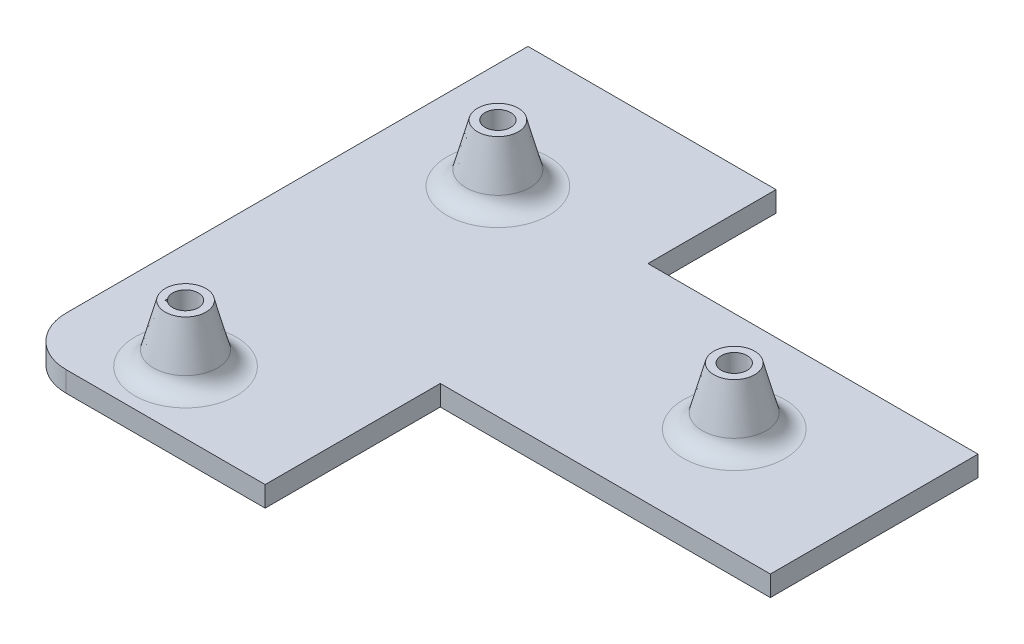
SolidWorks part; units mm, degrees
ref_plane "Front Plane" through (0, 0, 0) normal (0, 0, 1) x (1, 0, 0)
ref_plane "Top Plane" through (0, 0, 0) normal (0, 1, 0) x (1, 0, 0)
ref_plane "Right Plane" through (0, 0, 0) normal (1, 0, 0) x (0, 0, -1)
sketch "Backplane" plane through (0, 0, 0) normal (0, 1, 0) x (1, 0, 0)
  line L0 (-80.645, 87.63) -> (8.255, 87.63)
  line L1 (-106.045, -113.03) -> (106.045, -113.03)
  line L2 (-106.045, -113.03) -> (-106.045, 113.03)
  line L3 (-106.045, 113.03) -> (106.045, 113.03)
  line L4 (106.045, -113.03) -> (106.045, 113.03)
  line L5 (-106.045, -113.03) -> (106.045, 113.03) construction
  line L6 (-106.045, 113.03) -> (106.045, -113.03) construction
  line L7 (-106.045, 113.03) -> (-80.645, 113.03) construction
  line L8 (-106.045, 113.03) -> (-106.045, 87.63) construction
  line L9 (-106.045, 87.63) -> (-80.645, 87.63)
  line L10 (-80.645, 113.03) -> (-80.645, 87.63)
  line L11 (106.045, 113.03) -> (80.645, 113.03) construction
  line L12 (106.045, 113.03) -> (106.045, 87.63) construction
  line L13 (106.045, 87.63) -> (80.645, 87.63)
  line L14 (80.645, 113.03) -> (80.645, 87.63)
  line L15 (8.255, 87.63) -> (8.255, 113.03)
  point P0 (0, 0)
  dimension "D1" = 212.09
  dimension "D2" = 226.06
sketch "Protoboard1" plane through (0, 0, 0) normal (0, 1, 0) x (1, 0, 0)
  line L0 (59.2817, 74.5827) -> (59.2817, 49.1827) construction
  line L1 (-98.1983, 23.7827) -> (59.2817, 23.7827)
  line L2 (-98.1983, 23.7827) -> (-98.1983, 74.5827)
  line L3 (-98.1983, 74.5827) -> (59.2817, 74.5827)
  line L4 (59.2817, 23.7827) -> (59.2817, 74.5827)
  line L5 (-98.1983, 23.7827) -> (59.2817, 74.5827) construction
  line L6 (-98.1983, 74.5827) -> (59.2817, 23.7827) construction
  line L7 (-92.8897, 49.1827) -> (53.9731, 49.1827)
  line L8 (-19.4583, 49.1827) -> (-19.4583, 23.7827) construction
  line L9 (-92.8897, 49.1827) -> (-94.4772, 49.1827)
  circle A4 centre (-94.4772, 49.1827) radius 1.5875
  circle A5 centre (-94.4772, 49.1827) radius 5.5499
  circle A6 centre (55.5606, 49.1827) radius 1.5875
  circle A7 centre (55.5606, 49.1827) radius 5.5499
  circle A8 centre (-94.4772, 49.1827) radius 1.9939
  circle A9 centre (55.5606, 49.1827) radius 1.9939
  point P0 (-19.4583, 49.1827)
  point P9 (-19.4583, 49.1827)
  point P10 (-19.4583, 49.1827)
  dimension "D5" = 3.175
  dimension "D6" = 11.0998
  dimension "D7" = 3.9878
  dimension "D3" = 157.48
  dimension "D1" = 73.4314
  dimension "D2" = 1.5875
sketch "Protoboard2" plane through (0, 0, 0) normal (0, 1, 0) x (1, 0, 0)
  line L0 (58.42, 17.145) -> (58.42, -8.255) construction
  line L1 (-99.06, -33.655) -> (58.42, -33.655)
  line L2 (-99.06, -33.655) -> (-99.06, 17.145)
  line L3 (-99.06, 17.145) -> (58.42, 17.145)
  line L4 (58.42, -33.655) -> (58.42, 17.145)
  line L5 (-99.06, -33.655) -> (58.42, 17.145) construction
  line L6 (-99.06, 17.145) -> (58.42, -33.655) construction
  line L7 (-93.7514, -8.255) -> (53.1114, -8.255)
  line L8 (-20.32, -8.255) -> (-20.32, -33.655) construction
  line L9 (-93.7514, -8.255) -> (-95.3389, -8.255)
  circle A0 centre (-95.3389, -8.255) radius 1.5875
  circle A1 centre (-95.3389, -8.255) radius 5.5499
  circle A4 centre (-95.3389, -8.255) radius 1.9939
  circle A6 centre (54.6989, -8.255) radius 1.5875
  circle A7 centre (54.6989, -8.255) radius 1.9939
  circle A8 centre (54.6989, -8.255) radius 5.5499
  point P0 (-20.32, -8.255)
  point P9 (-20.32, -8.255)
  point P10 (-20.32, -8.255)
  dimension "D5" = 3.175
  dimension "D6" = 11.0998
  dimension "D7" = 3.9878
  dimension "D4" = 1.5875
  dimension "D1" = 157.48
  dimension "D3" = 73.4314
sketch "ADS1256" plane through (0, 0, 0) normal (0, 1, 0) x (1, 0, 0)
  line L0 (83.3697, -5.6387) -> (83.3697, 20.5868)
  line L1 (65.6786, -35.7758) -> (101.0608, -35.7758)
  line L2 (65.6786, -35.7758) -> (65.6786, 24.4984)
  line L3 (65.6786, 24.4984) -> (101.0608, 24.4984)
  line L4 (101.0608, -35.7758) -> (101.0608, 24.4984)
  line L5 (65.6786, -35.7758) -> (101.0608, 24.4984) construction
  line L6 (65.6786, 24.4984) -> (101.0608, -35.7758) construction
  line L7 (83.3697, 20.5868) -> (83.3697, 22.1743)
  line L8 (83.3697, 22.1743) -> (97.0222, 22.1743)
  line L9 (97.0222, 22.1743) -> (98.6097, 22.1743)
  line L10 (83.3697, -5.6387) -> (89.9657, -5.6387) construction
  circle A0 centre (98.6097, 22.1743) radius 1.5875
  circle A1 centre (98.6097, 22.1743) radius 5.5499
  circle A2 centre (68.1297, 22.1743) radius 1.5875
  circle A3 centre (68.1297, 22.1743) radius 5.5499
  circle A4 centre (98.6097, -33.4517) radius 5.5499
  circle A5 centre (98.6097, -33.4517) radius 1.5875
  circle A6 centre (68.1297, -33.4517) radius 1.5875
  circle A7 centre (68.1297, -33.4517) radius 5.5499
  circle A8 centre (98.6097, 22.1743) radius 1.9939
  circle A9 centre (68.1297, 22.1743) radius 1.9939
  circle A10 centre (98.6097, -33.4517) radius 1.9939
  circle A11 centre (68.1297, -33.4517) radius 1.9939
  point P0 (83.3697, -5.6387)
  dimension "D1" = 1.5875
  dimension "D2" = 1.5875
  dimension "D3" = 3.175
  dimension "D4" = 11.0998
  dimension "D5" = 3.9878
sketch "3V_Buck" plane through (0, 0, 0) normal (0, 1, 0) x (1, 0, 0)
  circle A0 centre (88.2115, 54.7666) radius 1.5875
  circle A1 centre (88.2115, 54.7666) radius 5.5499
  circle A2 centre (88.2115, 54.7666) radius 1.9939
  dimension "D1" = 3.175
  dimension "D2" = 11.0998
  dimension "D3" = 3.9878
sketch "Relay" plane through (0, 0, 0) normal (0, 1, 0) x (1, 0, 0)
  line L1 (16.3302, 81.8626) -> (66.6036, 81.8626)
  line L2 (16.3302, 81.8626) -> (16.3302, 108.1272)
  line L3 (16.3302, 108.1272) -> (66.6036, 108.1272)
  line L4 (66.6036, 81.8626) -> (66.6036, 108.1272)
  line L5 (16.3302, 81.8626) -> (66.6036, 108.1272) construction
  line L6 (16.3302, 108.1272) -> (66.6036, 81.8626) construction
  line L7 (41.4669, 94.9949) -> (41.4669, 104.2024)
  line L8 (41.4669, 104.2024) -> (41.4669, 105.7899)
  line L9 (41.4669, 105.7899) -> (62.1298, 105.7899)
  line L10 (62.1298, 105.7899) -> (63.7173, 105.7899)
  line L11 (41.4669, 94.9949) -> (31.7125, 94.9949) construction
  circle A0 centre (63.7173, 105.7899) radius 1.5875
  circle A1 centre (63.7173, 105.7899) radius 5.5499
  circle A2 centre (19.2165, 105.7899) radius 1.5875
  circle A3 centre (19.2165, 105.7899) radius 5.5499
  circle A4 centre (19.2165, 84.1999) radius 1.5875
  circle A5 centre (19.2165, 84.1999) radius 5.5499
  circle A6 centre (63.7173, 84.1999) radius 1.5875
  circle A7 centre (63.7173, 84.1999) radius 5.5499
  circle A8 centre (63.7173, 105.7899) radius 1.9939
  circle A9 centre (19.2165, 105.7899) radius 1.9939
  circle A10 centre (19.2165, 84.1999) radius 1.9939
  circle A11 centre (63.7173, 84.1999) radius 1.9939
  dimension "D4" = 3.175
  dimension "D5" = 11.0998
  dimension "D6" = 3.9878
  dimension "D1" = 1.5875
  dimension "D2" = 20.6629
  dimension "D3" = 1.5875
sketch "ServoBoard" plane through (0, 0, 0) normal (0, 1, 0) x (1, 0, 0)
  line L0 (-89.6011, -103.339) -> (-89.6011, -58.0508)
  line L1 (-103.5076, -105.5869) -> (-34.6228, -105.5869)
  line L2 (-103.5076, -105.5869) -> (-103.5076, -52.1961)
  line L3 (-103.5076, -52.1961) -> (-34.6228, -52.1961)
  line L4 (-34.6228, -105.5869) -> (-34.6228, -52.1961)
  line L5 (-103.5076, -105.5869) -> (-34.6228, -52.1961) construction
  line L6 (-103.5076, -52.1961) -> (-34.6228, -105.5869) construction
  line L7 (-103.5076, -105.5869) -> (-91.1886, -105.5869)
  line L8 (-103.5076, -105.5869) -> (-103.5076, -104.9265)
  line L9 (-103.5076, -104.9265) -> (-91.1886, -104.9265)
  line L10 (-91.1886, -105.5869) -> (-91.1886, -104.9265)
  line L11 (-91.1886, -104.9265) -> (-89.6011, -104.9265)
  line L12 (-91.1886, -104.9265) -> (-91.1886, -103.339)
  line L13 (-91.1886, -103.339) -> (-89.6011, -103.339)
  line L14 (-89.6011, -104.9265) -> (-89.6011, -103.339)
  line L15 (-89.6011, -58.0508) -> (-89.6011, -54.8758)
  line L16 (-89.6011, -103.339) -> (-38.6137, -69.1904)
  line L17 (-89.6011, -54.8758) -> (-38.6134, -69.1905)
  circle A0 centre (-89.6011, -103.339) radius 1.651
  circle A1 centre (-89.6011, -103.339) radius 1.9939
  circle A2 centre (-89.6011, -103.339) radius 5.5499
  circle A3 centre (-89.6011, -54.8758) radius 1.5875
  circle A4 centre (-89.6011, -54.8758) radius 1.9939
  circle A5 centre (-89.6011, -54.8758) radius 5.5499
  circle A6 centre (-38.6134, -69.1905) radius 1.5875
  circle A7 centre (-38.6137, -69.1904) radius 1.9939
  circle A8 centre (-38.6137, -69.1904) radius 5.5499
  point P0 (-69.0652, -78.8915)
  dimension "D3" = 1.5875
  dimension "D8" = 3.9878
  dimension "D9" = 11.0998
  dimension "D11" = 3.175
  dimension "D12" = 3.9878
  dimension "D13" = 11.0998
  dimension "D7" = 3.302
  dimension "D17" = 3.175
  dimension "D18" = 3.9878
  dimension "D19" = 11.0998
  dimension "D1" = 68.8848
  dimension "D2" = 53.3908
  dimension "D4" = 1.5875
  dimension "D5" = 12.319
  dimension "D6" = 0.6604
  dimension "D10" = 3.175
  dimension "D14" = 45.2882
  dimension "D15" = 74.318
  dimension "D16" = 56.188
sketch "Nucleo" plane through (0, 0, 0) normal (0, 1, 0) x (1, 0, 0)
  line L0 (73.7198, -98.0391) -> (73.7198, -49.7791)
  line L1 (-30.5599, -110.32) -> (102.7901, -110.32)
  line L2 (-30.5599, -110.32) -> (-30.5599, -40.6732)
  line L3 (-30.5599, -40.6732) -> (102.7901, -40.6732)
  line L4 (102.7901, -110.32) -> (102.7901, -40.6732)
  line L5 (-30.5599, -110.32) -> (102.7901, -40.6732) construction
  line L6 (-30.5599, -40.6732) -> (102.7901, -110.32) construction
  line L11 (102.7901, -110.32) -> (75.3073, -110.32)
  line L12 (102.7901, -110.32) -> (102.7901, -99.6266)
  line L13 (102.7901, -99.6266) -> (75.3073, -99.6266)
  line L14 (75.3073, -110.32) -> (75.3073, -99.6266)
  line L15 (75.3073, -99.6266) -> (73.7198, -99.6266)
  line L16 (75.3073, -99.6266) -> (75.3073, -98.0391)
  line L17 (75.3073, -98.0391) -> (73.7198, -98.0391)
  line L18 (73.7198, -99.6266) -> (73.7198, -98.0391)
  line L19 (73.7198, -98.0391) -> (-1.2702, -98.0391)
  line L20 (-1.2702, -98.0391) -> (-1.2702, -96.7691)
  line L21 (-1.2702, -96.7691) -> (-1.2702, -51.0491)
  circle A0 centre (73.7198, -98.0391) radius 1.5875
  circle A1 centre (73.7198, -98.0391) radius 1.9939
  circle A2 centre (73.7198, -98.0391) radius 5.5499
  circle A3 centre (73.7198, -49.7791) radius 1.5875
  circle A4 centre (73.7198, -49.7791) radius 1.9939
  circle A5 centre (73.7198, -49.7791) radius 5.5499
  circle A6 centre (-1.2702, -96.7691) radius 1.5875
  circle A7 centre (-1.2702, -96.7691) radius 1.9939
  circle A8 centre (-1.2702, -96.7691) radius 5.5499
  circle A9 centre (-1.2702, -51.0491) radius 1.5875
  circle A10 centre (-1.2702, -51.0491) radius 1.9939
  circle A11 centre (-1.2702, -51.0491) radius 5.5499
  point P0 (36.1151, -75.4966)
  dimension "D1" = 1.5875
  dimension "D2" = 1.5875
  dimension "D7" = 3.175
  dimension "D8" = 3.9878
  dimension "D9" = 11.0998
  dimension "D11" = 3.175
  dimension "D12" = 3.9878
  dimension "D13" = 11.0998
  dimension "D16" = 3.175
  dimension "D17" = 3.9878
  dimension "D18" = 11.0998
  dimension "D20" = 3.175
  dimension "D21" = 3.9878
  dimension "D22" = 11.0998
  dimension "D3" = 133.35
  dimension "D4" = 69.6468
  dimension "D5" = 27.4828
  dimension "D6" = 10.6934
  dimension "D10" = 48.26
  dimension "D14" = 74.99
  dimension "D15" = 1.27
  dimension "D19" = 45.72
extrude "Backplane_Extrude" add sketch "Backplane" against normal blind 3.175 contours L14 L3 L10 L9 L2 L1 L4 L13 region at (1.8409, 0, 8.0188)
fillet "Backplane_Fillets" radius 7.62 8 edges at (106.045, -1.5875, -87.63) (80.645, -1.5875, -87.63) (80.645, -1.5875, -113.03) (-106.045, -1.5875, -87.63) (106.045, -1.5875, 113.03) (-106.045, -1.5875, 113.03) (8.255, -1.5875, -113.03) (8.255, -1.5875, -87.63)
extrude "Boss-Extrude2" add sketch "Protoboard1" along normal blind 8.89 contours A8 A5 L2 | L2 A5 | A9 A7 L4 | A7 L4 region at (-98.9412, 0, -49.1827) region at (-98.0536, 0, -49.1827) region at (53.3666, 0, -44.2427) region at (60.0247, 0, -49.1827)
draft "Draft1" type of draft neutral plane draft angle 15 faces to draft 2 face at (55.5606, 8.89, -43.6328) face at (-94.4772, 8.89, -43.6328) neutral plane through (0, 0, 0) neutral plane normal (0, 1, 0) parameters "D1"=15
fillet "Fillet5" radius 3.048 2 edges at (55.5606, 0, -43.6328) (-94.4772, 0, -43.6328)
extrude "Boss-Extrude3" add sketch "Protoboard2" along normal blind 8.89 contours A4 A1 L2 | L2 A1 | A8 A7 L4 | A8 L4 region at (-99.8029, 0, 8.255) region at (-98.9154, 0, 8.255) region at (52.5049, 0, 13.195) region at (59.1629, 0, 8.255)
draft "Draft2" type of draft neutral plane draft angle 15 faces to draft 2 face at (54.6989, 8.89, 13.8049) face at (-95.3389, 8.89, 13.8049) neutral plane through (0, 0, 0) neutral plane normal (0, 1, 0) parameters "D1"=15
fillet "Fillet6" radius 3.048 2 edges at (54.6989, 0, 13.8049) (-95.3389, 0, 13.8049)
extrude "Boss-Extrude4" add sketch "ADS1256" along normal blind 8.89 contours A3 L3 L2 A9 | A3 L2 L3 | L4 A1 L3 | A8 A1 L4 L3 | A4 L4 L1 | A4 L1 L4 A10 | L1 A7 L2 A11 | L2 A7 L1 region at (69.706, 0, 31.7947) region at (69.4241, 0, 35.9251) region at (97.0334, 0, 31.7947) region at (97.3153, 0, 35.9251) region at (64.3596, 0, -26.0412) region at (69.706, 0, -20.5173) region at (97.0334, 0, -20.5173) region at (101.2101, 0, -20.8467)
draft "Draft3" type of draft neutral plane draft angle 15 faces to draft 4 face at (98.6097, 8.89, -16.6244) face at (98.6097, 8.89, 39.0016) face at (68.1297, 8.89, 39.0016) face at (68.1297, 8.89, -16.6244) neutral plane through (0, 0, 0) neutral plane normal (0, 1, 0) parameters "D1"=15
fillet "Fillet7" radius 3.048 4 edges at (98.6097, 0, 39.0016) (98.6097, 0, -16.6244) (68.1297, 0, -16.6244) (68.1297, 0, 39.0016)
extrude "Boss-Extrude5" add sketch "3V_Buck" along normal blind 8.89 contours A1 A2 region at (82.8185, 0, -54.7666)
draft "Draft4" type of draft neutral plane draft angle 15 faces to draft 1 face at (88.2115, 8.89, -49.2167) neutral plane through (0, 0, 0) neutral plane normal (0, 1, 0) parameters "D1"=15
fillet "Fillet8" radius 3.048 1 edges at (88.2115, 0, -49.2167)
extrude "Boss-Extrude6" add sketch "Relay" along normal blind 8.89 contours A3 L3 L2 A9 | A3 L2 L3 | A8 A1 L4 L3 | L4 A1 L3 | A7 L4 L1 | A7 L1 L4 A11 | L1 A5 L2 A10 | L2 A5 L1 region at (20.5049, 0, -85.8218) region at (20.2902, 0, -81.715) region at (62.429, 0, -85.8218) region at (62.6436, 0, -81.715) region at (15.6168, 0, -109.8181) region at (20.5049, 0, -104.168) region at (62.429, 0, -104.168) region at (66.7513, 0, -104.5884)
draft "Draft5" type of draft neutral plane draft angle 15 faces to draft 4 face at (19.2165, 8.89, -78.65) face at (63.7173, 8.89, -78.65) face at (63.7173, 8.89, -100.24) face at (19.2165, 8.89, -100.24) neutral plane through (0, 0, 0) neutral plane normal (0, 1, 0) parameters "D1"=15
fillet "Fillet9" radius 3.048 4 edges at (19.2165, 0, -78.65) (63.7173, 0, -78.65) (63.7173, 0, -100.24) (19.2165, 0, -100.24)
extrude "Boss-Extrude7" add sketch "ServoBoard" along normal blind 8.89 contours L0 A5 L17 A4 L15 | L17 A5 L3 L0 L15 A4 | L3 A5 | L4 A8 | L4 A8 L17 A7 L16 | L17 A8 L16 A7 | L1 A2 L16 A1 L11 L10 | L7 A2 L1 | L0 A2 L9 L12 A1 | L16 A2 L0 A1 | L9 A2 L7 L10 region at (-92.4087, 0, 101.4937) region at (-87.7688, 0, 99.9065) region at (-86.2185, 0, 103.5104) region at (-94.2609, 0, 57.6277) region at (-87.3219, 0, 57.8828) region at (-92.9975, 0, 105.253) region at (-42.4911, 0, 69.809) region at (-41.6669, 0, 71.4099) region at (-89.6011, 0, 51.018) region at (-89.6011, 0, 106.9485) region at (-33.991, 0, 69.1904)
draft "Draft6" type of draft neutral plane draft angle 15 faces to draft 3 face at (-89.6011, 8.89, 60.4257) face at (-38.6137, 8.89, 74.7403) face at (-89.6011, 8.89, 108.8889) neutral plane through (0, 0, 0) neutral plane normal (0, 1, 0) parameters "D1"=15
fillet "Fillet10" radius 3.048 3 edges at (-89.6011, 0, 108.8889) (-38.6137, 0, 74.7403) (-89.6011, 0, 60.4257)
extrude "Boss-Extrude8" add sketch "Nucleo" along normal blind 8.89 contours A11 A10 | A5 A4 | L13 A2 L0 A1 L16 | L0 A2 L19 A1 | L19 A2 L14 L15 A1 | L14 A2 L13 | L21 A8 L19 A7 | L19 A8 L21 A7 region at (71.1407, 0, 95.46) region at (76.5275, 0, 96.1938) region at (71.8745, 0, 100.8467) region at (69.9064, 0, 45.9657) region at (-5.0836, 0, 47.2357) region at (-5.4982, 0, 100.1185) region at (1.5063, 0, 94.7714) region at (76.7573, 0, 101.0766)
draft "Draft7" type of draft neutral plane draft angle 15 faces to draft 4 face at (73.7198, 8.89, 103.589) face at (73.7198, 8.89, 55.329) face at (-1.2702, 8.89, 56.599) face at (-1.2702, 8.89, 102.319) neutral plane through (0, 0, 0) neutral plane normal (0, 1, 0) parameters "D1"=15
fillet "Fillet11" radius 3.048 4 edges at (73.7198, 0, 103.589) (73.7198, 0, 55.329) (-1.2702, 0, 56.599) (-1.2702, 0, 102.319)
sketch "Sketch1" plane through (0, 0, 0) normal (0, 1, 0) x (1, 0, 0)
  line L1 (-116.239, -33.7617) -> (-16.3413, -33.7617)
  line L2 (-116.239, -33.7617) -> (-116.239, -117.3181)
  line L3 (-116.239, -117.3181) -> (-16.3413, -117.3181)
  line L4 (-16.3413, -33.7617) -> (-16.3413, -117.3181)
extrude "Cut-Extrude1" cut sketch "Sketch1" against normal mid plane 19.05 flip side to cut
sketch "Sketch2" plane through (0, 0, 0) normal (0, 1, 0) x (1, 0, 0)
  line L1 (-6.0685, -119.449) -> (-67.5557, -119.449)
  line L2 (-6.0685, -119.449) -> (-6.0685, -85.857)
  line L3 (-6.0685, -85.857) -> (-67.5557, -85.857)
  line L4 (-67.5557, -119.449) -> (-67.5557, -85.857)
  line L5 (-67.5557, -15.1369) -> (-6.0685, -15.1369)
  line L6 (-67.5557, -15.1369) -> (-67.5557, -53.64)
  line L7 (-67.5557, -53.64) -> (-6.0685, -53.64)
  line L8 (-6.0685, -15.1369) -> (-6.0685, -53.64)
extrude "Cut-Extrude2" cut sketch "Sketch2" against normal mid plane 19.05
equation "\"D2@Relay\"=1.627/2"
equation "\"D1@Protoboard1\" = 5.782 / 2"
equation "\"M3_PCB_Hole_Diam\"= 0.125in"
equation "\"M3_Insert_OuterFeature_Diam\"= \"M3_Print_CAD_Hole_Diam\" + ( 0.14 * 2 )"
equation "\"D2@Protoboard1\" = \"M3_PCB_Hole_Diam\" / 2"
equation "\"D5@Protoboard1\" = \"M3_PCB_Hole_Diam\""
equation "\"D6@Protoboard1\" = \"M3_Insert_OuterFeature_Diam\""
equation "\"D1@Relay\"=\"M3_PCB_Hole_Diam\"/2"
equation "\"D3@Relay\"=\"M3_PCB_Hole_Diam\"/2"
equation "\"D4@Relay\"=\"M3_PCB_Hole_Diam\""
equation "\"D5@Relay\"=\"M3_Insert_OuterFeature_Diam\""
equation "\"D1@ADS1256\"=\"M3_PCB_Hole_Diam\"/2"
equation "\"D2@ADS1256\"=\"M3_PCB_Hole_Diam\"/2"
equation "\"D3@ADS1256\"=\"M3_PCB_Hole_Diam\""
equation "\"D4@ADS1256\"=\"M3_Insert_OuterFeature_Diam\""
equation "\"M3_Print_CAD_Hole_Diam\"= 0.157in"
equation "\"D5@ADS1256\"=\"M3_Print_CAD_Hole_Diam\""
equation "\"D7@Protoboard1\" = \"M3_Print_CAD_Hole_Diam\""
equation "\"D6@Relay\"=\"M3_Print_CAD_Hole_Diam\""
equation "\"D3@3V_Buck\"=\"M3_Print_CAD_Hole_Diam\""
equation "\"D1@3V_Buck\"=\"M3_PCB_Hole_Diam\""
equation "\"D1@Nucleo\"=\"M3_PCB_Hole_Diam\"/2"
equation "\"D2@Nucleo\"=\"M3_PCB_Hole_Diam\"/2"
equation "\"D7@Nucleo\"=\"M3_PCB_Hole_Diam\""
equation "\"D8@Nucleo\"=\"M3_Print_CAD_Hole_Diam\""
equation "\"D9@Nucleo\"=\"M3_Insert_OuterFeature_Diam\""
equation "\"D11@Nucleo\"=\"M3_PCB_Hole_Diam\""
equation "\"D12@Nucleo\"=\"M3_Print_CAD_Hole_Diam\""
equation "\"D13@Nucleo\"=\"M3_Insert_OuterFeature_Diam\""
equation "\"D16@Nucleo\"=\"M3_PCB_Hole_Diam\""
equation "\"D17@Nucleo\"=\"M3_Print_CAD_Hole_Diam\""
equation "\"D18@Nucleo\"=\"M3_Insert_OuterFeature_Diam\""
equation "\"D20@Nucleo\"=\"M3_PCB_Hole_Diam\""
equation "\"D21@Nucleo\"=\"M3_Print_CAD_Hole_Diam\""
equation "\"D22@Nucleo\"=\"M3_Insert_OuterFeature_Diam\""
equation "\"D14@Nucleo\"=133.4mm-12.7mm-16.51mm-3.8mm-2.54mm-22.86mm"
equation "\"D19@Nucleo\"=45.72mm"
equation "\"D3@ServoBoard\"=\"M3_PCB_Hole_Diam\"/2"
equation "\"D4@ServoBoard\"=\"M3_PCB_Hole_Diam\"/2"
equation "\"D8@ServoBoard\"=\"M3_Print_CAD_Hole_Diam\""
equation "\"D9@ServoBoard\"=\"M3_Insert_OuterFeature_Diam\""
equation "\"D10@ServoBoard\"=\"M3_PCB_Hole_Diam\""
equation "\"D11@ServoBoard\"=\"M3_PCB_Hole_Diam\""
equation "\"D12@ServoBoard\"=\"M3_Print_CAD_Hole_Diam\""
equation "\"D13@ServoBoard\"=\"M3_Insert_OuterFeature_Diam\""
equation "\"D17@ServoBoard\"=\"M3_PCB_Hole_Diam\""
equation "\"D18@ServoBoard\"=\"M3_Print_CAD_Hole_Diam\""
equation "\"D19@ServoBoard\"=\"M3_Insert_OuterFeature_Diam\""
equation "\"M3_Insert_OuterFeature_DraftAngle\"= 15deg"
equation "\"D1@Draft1\"=\"M3_Insert_OuterFeature_DraftAngle\""
equation "\"M3_Insert_OuterFeature_FilletRad\"= 0.12in"
equation "\"D1@Fillet5\"=\"M3_Insert_OuterFeature_FilletRad\""
equation "\"M3_Insert_OuterFeature_ExtrudeHt\"= 0.35in"
equation "\"D1@Boss-Extrude2\"=\"M3_Insert_OuterFeature_ExtrudeHt\""
equation "\"D6@Protoboard2\"=\"M3_Insert_OuterFeature_Diam\""
equation "\"D5@Protoboard2\"=\"M3_PCB_Hole_Diam\""
equation "\"D7@Protoboard2\"=\"M3_Print_CAD_Hole_Diam\""
equation "\"D1@Boss-Extrude3\"=\"M3_Insert_OuterFeature_ExtrudeHt\""
equation "\"D1@Draft2\"=\"M3_Insert_OuterFeature_DraftAngle\""
equation "\"D1@Fillet6\"=\"M3_Insert_OuterFeature_FilletRad\""
equation "\"D1@Boss-Extrude4\"=\"M3_Insert_OuterFeature_ExtrudeHt\""
equation "\"D1@Draft3\"=\"M3_Insert_OuterFeature_DraftAngle\""
equation "\"D1@Fillet7\"=\"M3_Insert_OuterFeature_FilletRad\""
equation "\"D1@Boss-Extrude5\"=\"M3_Insert_OuterFeature_ExtrudeHt\""
equation "\"D1@Draft4\"=\"M3_Insert_OuterFeature_DraftAngle\""
equation "\"D2@3V_Buck\"=\"M3_Insert_OuterFeature_Diam\""
equation "\"D1@Fillet8\"=\"M3_Insert_OuterFeature_FilletRad\""
equation "\"D1@Boss-Extrude6\"=\"M3_Insert_OuterFeature_ExtrudeHt\""
equation "\"D1@Draft5\"=\"M3_Insert_OuterFeature_DraftAngle\""
equation "\"D1@Fillet9\"=\"M3_Insert_OuterFeature_FilletRad\""
equation "\"D1@Boss-Extrude7\"=\"M3_Insert_OuterFeature_ExtrudeHt\""
equation "\"D1@Draft6\"=\"M3_Insert_OuterFeature_DraftAngle\""
equation "\"D1@Fillet10\"=\"M3_Insert_OuterFeature_FilletRad\""
equation "\"D1@Boss-Extrude8\"=\"M3_Insert_OuterFeature_ExtrudeHt\""
equation "\"D1@Fillet11\"=\"M3_Insert_OuterFeature_FilletRad\""
equation "\"D1@Draft7\"=\"M3_Insert_OuterFeature_DraftAngle\""
